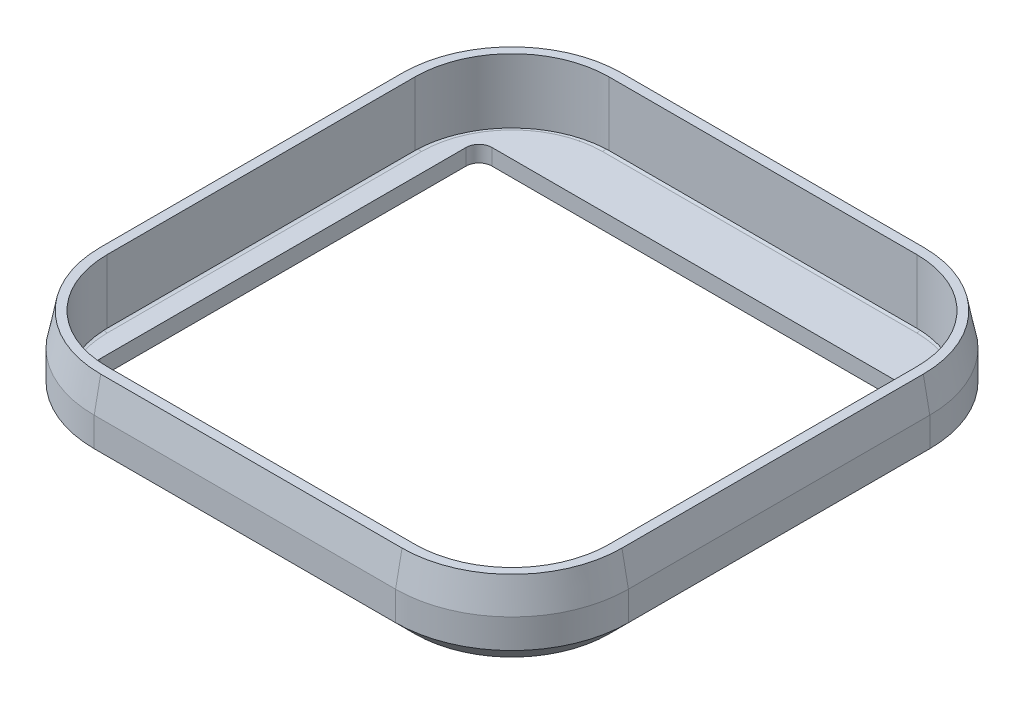
SolidWorks part; units mm, degrees
ref_plane "Front Plane" through (0, 0, 0) normal (0, 0, 1) x (1, 0, 0)
ref_plane "Top Plane" through (0, 0, 0) normal (0, 1, 0) x (1, 0, 0)
ref_plane "Right Plane" through (0, 0, 0) normal (1, 0, 0) x (0, 0, -1)
sketch "Sketch1" plane through (0, 0, 0) normal (0, 1, 0) x (1, 0, 0)
  line L0 (-32.7122, 35.1092) -> (19.2878, 35.1092)
  line L1 (-43.7122, 24.1092) -> (-43.7122, -27.8908)
  line L2 (-32.7122, -38.8908) -> (19.2878, -38.8908)
  line L3 (30.2878, 24.1092) -> (30.2878, -27.8908)
  line L4 (-33.2122, 32.6092) -> (19.7878, 32.6092)
  line L5 (-41.2122, 24.6092) -> (-41.2122, -28.3908)
  line L6 (-33.2122, -36.3908) -> (19.7878, -36.3908)
  line L7 (27.7878, 24.6092) -> (27.7878, -28.3908)
  line L8 (-33.0122, 35.4092) -> (19.5878, 35.4092)
  line L9 (-44.0122, 24.4092) -> (-44.0122, -28.1908)
  line L10 (-33.0122, -39.1908) -> (19.5878, -39.1908)
  line L11 (30.5878, 24.4092) -> (30.5878, -28.1908)
  line L12 (-31.0122, 37.4092) -> (17.5878, 37.4092)
  line L13 (-46.0122, 22.4092) -> (-46.0122, -26.1908)
  line L14 (-31.0122, -41.1908) -> (17.5878, -41.1908)
  line L15 (32.5878, 22.4092) -> (32.5878, -26.1908)
  line L17 (-30.0122, 39.4092) -> (16.5878, 39.4092)
  line L18 (-48.0122, 21.4092) -> (-48.0122, -25.1908)
  line L19 (-30.0122, -43.1908) -> (16.5878, -43.1908)
  line L20 (34.5878, 21.4092) -> (34.5878, -25.1908)
  arc A0 (19.7878, 32.6092) -> (27.7878, 24.6092) centre (19.7878, 24.6092) cw
  arc A1 (19.7878, -36.3908) -> (27.7878, -28.3908) centre (19.7878, -28.3908) ccw
  arc A2 (-41.2122, -28.3908) -> (-33.2122, -36.3908) centre (-33.2122, -28.3908) ccw
  arc A3 (-33.2122, 32.6092) -> (-41.2122, 24.6092) centre (-33.2122, 24.6092) ccw
  arc A4 (-43.7122, -27.8908) -> (-32.7122, -38.8908) centre (-32.7122, -27.8908) ccw
  arc A5 (19.2878, -38.8908) -> (30.2878, -27.8908) centre (19.2878, -27.8908) ccw
  arc A6 (19.2878, 35.1092) -> (30.2878, 24.1092) centre (19.2878, 24.1092) cw
  arc A7 (-32.7122, 35.1092) -> (-43.7122, 24.1092) centre (-32.7122, 24.1092) ccw
  arc A8 (-44.0122, -28.1908) -> (-33.0122, -39.1908) centre (-33.0122, -28.1908) ccw
  arc A9 (19.5878, -39.1908) -> (30.5878, -28.1908) centre (19.5878, -28.1908) ccw
  arc A10 (19.5878, 35.4092) -> (30.5878, 24.4092) centre (19.5878, 24.4092) cw
  arc A11 (-33.0122, 35.4092) -> (-44.0122, 24.4092) centre (-33.0122, 24.4092) ccw
  arc A12 (-46.0122, -26.1908) -> (-31.0122, -41.1908) centre (-31.0122, -26.1908) ccw
  arc A13 (17.5878, -41.1908) -> (32.5878, -26.1908) centre (17.5878, -26.1908) ccw
  arc A14 (17.5878, 37.4092) -> (32.5878, 22.4092) centre (17.5878, 22.4092) cw
  arc A15 (-31.0122, 37.4092) -> (-46.0122, 22.4092) centre (-31.0122, 22.4092) ccw
  arc A16 (-48.0122, -25.1908) -> (-30.0122, -43.1908) centre (-30.0122, -25.1908) ccw
  arc A17 (16.5878, -43.1908) -> (34.5878, -25.1908) centre (16.5878, -25.1908) ccw
  arc A18 (16.5878, 39.4092) -> (34.5878, 21.4092) centre (16.5878, 21.4092) cw
  arc A19 (-30.0122, 39.4092) -> (-48.0122, 21.4092) centre (-30.0122, 21.4092) ccw
  dimension "D5" = 8
  dimension "D6" = 11
  dimension "D11" = 11
  dimension "D16" = 15
  dimension "D21" = 18
  dimension "D1" = 2.5
  dimension "D2" = 2.5
  dimension "D3" = 2.5
  dimension "D4" = 2.5
  dimension "D7" = 0.3
  dimension "D8" = 0.3
  dimension "D9" = 0.3
  dimension "D10" = 0.3
  dimension "D12" = 2
  dimension "D13" = 2
  dimension "D14" = 2
  dimension "D15" = 2
  dimension "D17" = 2
  dimension "D18" = 2
  dimension "D19" = 2
  dimension "D20" = 2
extrude "Boss-Extrude1" add sketch "Sketch1" along normal blind 12 contours L17 A19 L18 A16 L19 A17 L20 A18 A15 L12 A14 L15 A13 L14 A12 L13 region at (-6.7122, 0, -38.2411)
extrude "Boss-Extrude2" add sketch "Sketch1<3>" along normal blind 2 contours L12 A15 L13 A12 L14 A13 L15 A14 A11 L8 A10 L11 A9 L10 A8 L9 region at (-6.7122, 0, -36.2977)
sketch "Sketch1<3>" plane through (0, 0, 0) normal (0, 1, 0) x (1, 0, 0) same geometry as "Sketch1"
sketch "Sketch2" plane through (0, 0, 0) normal (0, -1, 0) x (1, 0, 0)
  line L0 (-43.9653, -28.4092) -> (31.6458, -28.4092)
  line L1 (31.6458, -28.4092) -> (28.9621, -33.2296)
  line L2 (28.9621, -33.2296) -> (23.4543, -35.9231)
  line L3 (23.4543, -35.9231) -> (-39.2676, -35.9231)
  line L4 (-39.2676, -35.9231) -> (-41.5964, -34.2618)
  line L5 (-41.5964, -34.2618) -> (-43.9653, -28.4092)
  line L6 (-43.4643, 32.1908) -> (31.9867, 32.1908)
  line L7 (31.9867, 32.1908) -> (24.0848, 40.9065)
  line L8 (24.0848, 40.9065) -> (12.9324, 40.9065)
  line L9 (12.9324, 40.9065) -> (-33.3209, 40.9065)
  line L10 (-33.3209, 40.9065) -> (-40.9681, 37.8113)
  line L11 (-40.9681, 37.8113) -> (-43.4643, 32.1908)
  line L12 (-33.0122, 39.1908) -> (19.5878, 39.1908) construction
  line L13 (-33.0122, -35.4092) -> (19.5878, -35.4092) construction
  dimension "D1" = 7
  dimension "D2" = 7
extrude "Boss-Extrude3" add sketch "Sketch2" against normal blind 2
fillet "Fillet1" radius 1 8 edges at (-6.7122, 2, -37.4092) (28.1944, 2, -33.0158) (32.5878, 2, 1.8908) (28.1944, 2, 36.7974) (-6.7122, 2, 41.1908) (-41.6188, 2, 36.7974) (-46.0122, 2, 1.8908) (-41.6188, 2, -33.0158)
chamfer "Chamfer2" distance 5 distance2 1 8 edges at (34.5878, 12, 1.8908) (29.3157, 12, -34.1372) (29.3157, 12, 37.9187) (-6.7122, 12, -39.4092) (-6.7122, 12, 43.1908) (-42.7401, 12, -34.1372) (-42.7401, 12, 37.9187) (-48.0122, 12, 1.8908) first distance on face at (34.5878, 6, 1.8908) first distance on face at (27.4518, 6, -32.2732) first distance on face at (27.4518, 6, 36.0547) first distance on face at (-6.7122, 6, -39.4092) first distance on face at (-6.7122, 6, 43.1908) first distance on face at (-40.8762, 6, -32.2732) first distance on face at (-40.8762, 6, 36.0547) first distance on face at (-48.0122, 6, 1.8908)
sketch "Sketch3" plane through (0, 0, 0) normal (0, -1, 0) x (1, 0, 0)
  line L0 (29.8347, -28.4092) -> (-43.2592, -28.4092) construction
  line L1 (30.6041, 32.4991) -> (28.7681, 32.4991)
  line L2 (30.6041, 32.4991) -> (30.6041, -28.7428)
  line L3 (30.6041, -28.7428) -> (28.7681, -28.7428)
  line L4 (28.7681, 32.4991) -> (28.7681, -28.7428)
  line L5 (-44.1147, 32.4991) -> (-42.1121, 32.4991)
  line L6 (-44.1147, 32.4991) -> (-44.1147, -28.4092)
  line L7 (-44.1147, -28.4092) -> (-42.1121, -28.4092)
  line L8 (-42.1121, 32.4991) -> (-42.1121, -28.4092)
extrude "Boss-Extrude4" add sketch "Sketch3" against normal up to vertex (2 mm away) up to point (30.5878, 2, 28.1908)
fillet "Fillet2" radius 2 4 edges at (-42.1121, 1, 32.1908) (-42.1121, 1, -28.4092) (28.7681, 1, -28.4092) (28.7681, 1, 32.1908)
sketch "Sketch4" plane through (0, 0, 0) normal (0, -1, 0) x (1, 0, 0)
  line L4 (-40.1121, -28.4092) -> (26.7681, -28.4092)
  line L5 (-42.1121, 30.1908) -> (-42.1121, -26.4092)
  line L6 (26.7681, 32.1908) -> (-40.1121, 32.1908)
  line L7 (28.7681, -26.4092) -> (28.7681, 30.1908)
  line L8 (-40.1121, -28.4092) -> (26.7681, -28.4092)
  line L9 (-42.1121, 30.1908) -> (-42.1121, -26.4092)
  line L10 (26.7681, 32.1908) -> (-40.1121, 32.1908)
  line L11 (28.7681, -26.4092) -> (28.7681, 30.1908)
  line L12 (-30.0122, -39.4092) -> (16.5878, -39.4092)
  line L13 (34.5878, -21.4092) -> (34.5878, 25.1908)
  line L14 (16.5878, 43.1908) -> (-30.0122, 43.1908)
  line L15 (-48.0122, 25.1908) -> (-48.0122, -21.4092)
  line L16 (-30.0122, -39.4092) -> (16.5878, -39.4092)
  line L17 (34.5878, -21.4092) -> (34.5878, 25.1908)
  line L18 (16.5878, 43.1908) -> (-30.0122, 43.1908)
  line L19 (-48.0122, 25.1908) -> (-48.0122, -21.4092)
  arc A4 (-42.1121, -26.4092) -> (-40.1121, -28.4092) centre (-40.1121, -26.4092) ccw
  arc A5 (-40.1121, 32.1908) -> (-42.1121, 30.1908) centre (-40.1121, 30.1908) ccw
  arc A6 (28.7681, 30.1908) -> (26.7681, 32.1908) centre (26.7681, 30.1908) ccw
  arc A7 (26.7681, -28.4092) -> (28.7681, -26.4092) centre (26.7681, -26.4092) ccw
  arc A8 (-42.1121, -26.4092) -> (-40.1121, -28.4092) centre (-40.1121, -26.4092) ccw
  arc A9 (-40.1121, 32.1908) -> (-42.1121, 30.1908) centre (-40.1121, 30.1908) ccw
  arc A10 (28.7681, 30.1908) -> (26.7681, 32.1908) centre (26.7681, 30.1908) ccw
  arc A11 (26.7681, -28.4092) -> (28.7681, -26.4092) centre (26.7681, -26.4092) ccw
  arc A12 (16.5878, -39.4092) -> (34.5878, -21.4092) centre (16.5878, -21.4092) ccw
  arc A13 (34.5878, 25.1908) -> (16.5878, 43.1908) centre (16.5878, 25.1908) ccw
  arc A14 (-30.0122, 43.1908) -> (-48.0122, 25.1908) centre (-30.0122, 25.1908) ccw
  arc A15 (-48.0122, -21.4092) -> (-30.0122, -39.4092) centre (-30.0122, -21.4092) ccw
  arc A16 (16.5878, -39.4092) -> (34.5878, -21.4092) centre (16.5878, -21.4092) ccw
  arc A17 (34.5878, 25.1908) -> (16.5878, 43.1908) centre (16.5878, 25.1908) ccw
  arc A18 (-30.0122, 43.1908) -> (-48.0122, 25.1908) centre (-30.0122, 25.1908) ccw
  arc A19 (-48.0122, -21.4092) -> (-30.0122, -39.4092) centre (-30.0122, -21.4092) ccw
  dimension "D1" = 0
  dimension "D2" = 0
extrude "Boss-Extrude6" add sketch "Sketch4" along normal blind 0.5
chamfer "Chamfer3" distance 3 angle 45 8 edges at (29.3157, -0.5, -34.1372) (34.5878, -0.5, 1.8908) (-6.7122, -0.5, -39.4092) (29.3157, -0.5, 37.9187) (-42.7401, -0.5, -34.1372) (-6.7122, -0.5, 43.1908) (-48.0122, -0.5, 1.8908) (-42.7401, -0.5, 37.9187)
sketch "Sketch5" plane through (0, 12, 0) normal (0, 1, 0) x (1, 0, 0)
  line L0 (17.5878, -41.1908) -> (-31.0122, -41.1908) construction
  line L1 (-30.5122, 36.9092) -> (17.0878, 36.9092)
  line L2 (-45.5122, 21.9092) -> (-45.5122, -25.6908)
  line L3 (-30.5122, -40.6908) -> (17.0878, -40.6908)
  line L4 (32.0878, 21.9092) -> (32.0878, -25.6908)
  line L6 (-31.0122, 37.4092) -> (17.5878, 37.4092) construction
  line L8 (32.5878, 22.4092) -> (32.5878, -26.1908) construction
  line L9 (-46.0122, 22.4092) -> (-46.0122, -26.1908) construction
  line L14 (17.5878, 37.4092) -> (-31.0122, 37.4092)
  line L15 (32.5878, -26.1908) -> (32.5878, 22.4092)
  line L16 (-31.0122, -41.1908) -> (17.5878, -41.1908)
  line L17 (-46.0122, 22.4092) -> (-46.0122, -26.1908)
  line L18 (17.5878, 37.4092) -> (-31.0122, 37.4092)
  line L19 (32.5878, -26.1908) -> (32.5878, 22.4092)
  line L20 (-31.0122, -41.1908) -> (17.5878, -41.1908)
  line L21 (-46.0122, 22.4092) -> (-46.0122, -26.1908)
  arc A0 (17.0878, -40.6908) -> (32.0878, -25.6908) centre (17.0878, -25.6908) ccw
  arc A1 (17.0878, 36.9092) -> (32.0878, 21.9092) centre (17.0878, 21.9092) cw
  arc A2 (-30.5122, 36.9092) -> (-45.5122, 21.9092) centre (-30.5122, 21.9092) ccw
  arc A3 (-45.5122, -25.6908) -> (-30.5122, -40.6908) centre (-30.5122, -25.6908) ccw
  arc A8 (-31.0122, 37.4092) -> (-46.0122, 22.4092) centre (-31.0122, 22.4092) ccw
  arc A9 (32.5878, 22.4092) -> (17.5878, 37.4092) centre (17.5878, 22.4092) ccw
  arc A10 (17.5878, -41.1908) -> (32.5878, -26.1908) centre (17.5878, -26.1908) ccw
  arc A11 (-46.0122, -26.1908) -> (-31.0122, -41.1908) centre (-31.0122, -26.1908) ccw
  arc A12 (-31.0122, 37.4092) -> (-46.0122, 22.4092) centre (-31.0122, 22.4092) ccw
  arc A13 (32.5878, 22.4092) -> (17.5878, 37.4092) centre (17.5878, 22.4092) ccw
  arc A14 (17.5878, -41.1908) -> (32.5878, -26.1908) centre (17.5878, -26.1908) ccw
  arc A15 (-46.0122, -26.1908) -> (-31.0122, -41.1908) centre (-31.0122, -26.1908) ccw
  dimension "D5" = 15
  dimension "D1" = 0.5
  dimension "D2" = 0.5
  dimension "D3" = 0.5
  dimension "D4" = 0.5
  dimension "D6" = 0
extrude "Boss-Extrude7" add sketch "Sketch5" against normal up to surface (10 mm away) up to face at (-6.672, 2, 1.8908)
